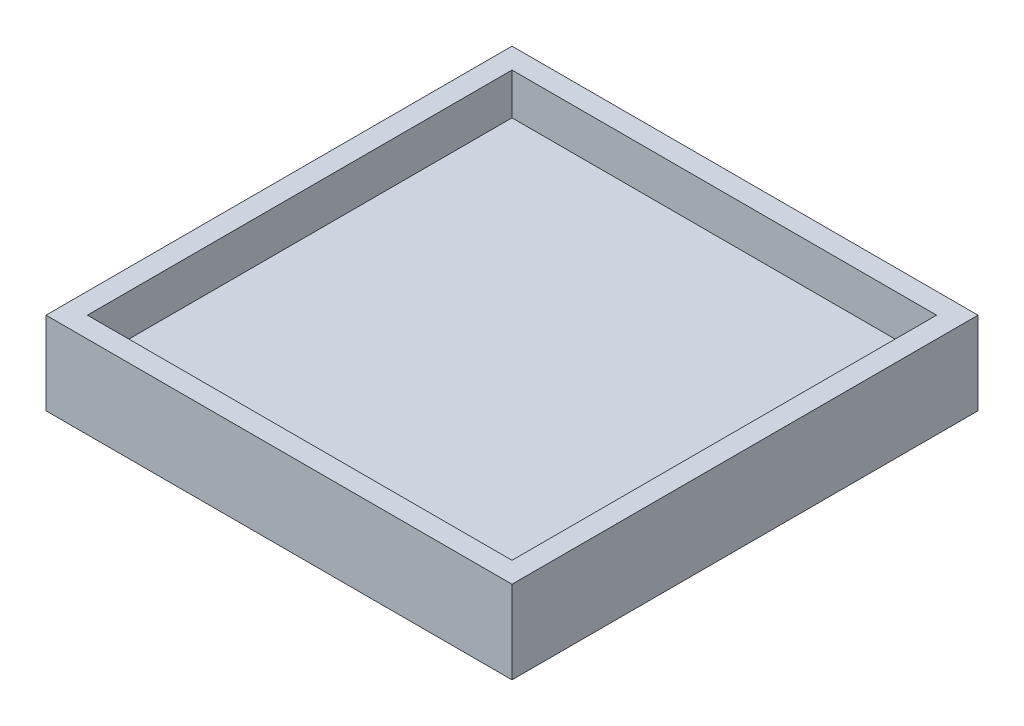
SolidWorks part; units mm, degrees
ref_plane "Front Plane" through (0, 0, 0) normal (0, 0, 1) x (1, 0, 0)
ref_plane "Top Plane" through (0, 0, 0) normal (0, 1, 0) x (1, 0, 0)
ref_plane "Right Plane" through (0, 0, 0) normal (1, 0, 0) x (0, 0, -1)
sketch "Sketch1" plane through (0, 0, 0) normal (0, 1, 0) x (1, 0, 0)
  line L1 (92, 100) -> (-133, 100)
  line L2 (92, 100) -> (92, -125)
  line L3 (92, -125) -> (-133, -125)
  line L4 (-133, 100) -> (-133, -125)
  line L7 (82, 90) -> (-123, 90)
  line L8 (82, 90) -> (82, -115)
  line L9 (82, -115) -> (-123, -115)
  line L10 (-123, 90) -> (-123, -115)
  point P0 (0, 0)
  point P6 (0, 0)
  dimension "D1" = 225
  dimension "D2" = 225
  dimension "D3" = 10
  dimension "D4" = 10
  dimension "D5" = 10
  dimension "D6" = 205
extrude "Walls" add sketch "Sketch1" along normal blind 40 contours L1 L4 L3 L2 L10 L7 L8 L9 region at (88.818, 0, 12.5)
extrude "Boss-Extrude2" add sketch "Sketch1<5>" along normal blind 20 contours L7 L10 L9 L8 region at (-20.5, 0, 12.5)
sketch "Sketch1<5>" plane through (0, 0, 0) normal (0, 1, 0) x (1, 0, 0) same geometry as "Sketch1"
equation "\"hight\"=110"
equation "\"D5@Sketch1\"=\"D4@Sketch1\""
equation "\"D3@Sketch1\"=\"D5@Sketch1\""
